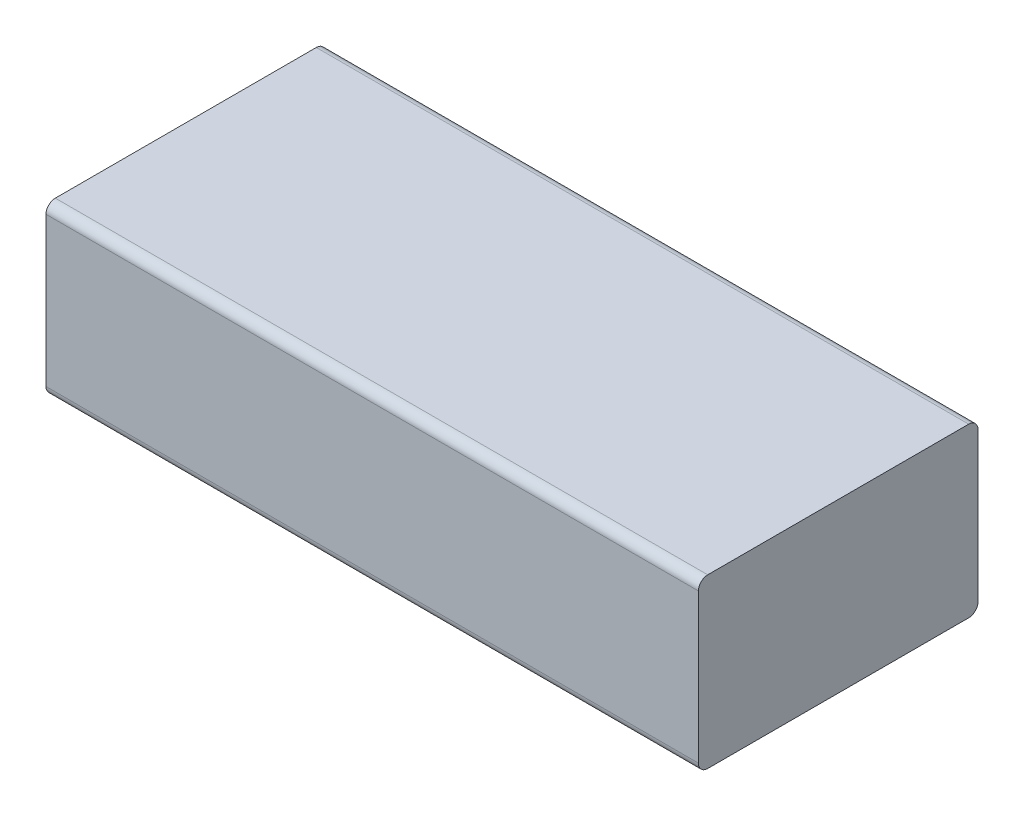
SolidWorks part; units mm, degrees
ref_plane "Front" through (0, 0, 0) normal (0, 0, 1) x (1, 0, 0)
ref_plane "Top" through (0, 0, 0) normal (0, 1, 0) x (1, 0, 0)
ref_plane "Right" through (0, 0, 0) normal (1, 0, 0) x (0, 0, -1)
sketch "Sketch1" plane through (0, 0, 0) normal (0, 1, 0) x (1, 0, 0)
  line L1 (-44.45, -19.05) -> (44.45, -19.05)
  line L2 (-44.45, -19.05) -> (-44.45, 19.05)
  line L3 (-44.45, 19.05) -> (44.45, 19.05)
  line L4 (44.45, -19.05) -> (44.45, 19.05)
  line L5 (-44.45, -19.05) -> (44.45, 19.05) construction
  line L6 (-44.45, 19.05) -> (44.45, -19.05) construction
  point P0 (0, 0)
  dimension "D1" = 88.9
  dimension "D2" = 38.1
extrude "Boss-Extrude1" add sketch "Sketch1" along normal blind 22.86
fillet "Fillet1" radius 1.27 4 edges at (0, 0, -19.05) (0, 0, 19.05) (0, 22.86, -19.05) (0, 22.86, 19.05)
